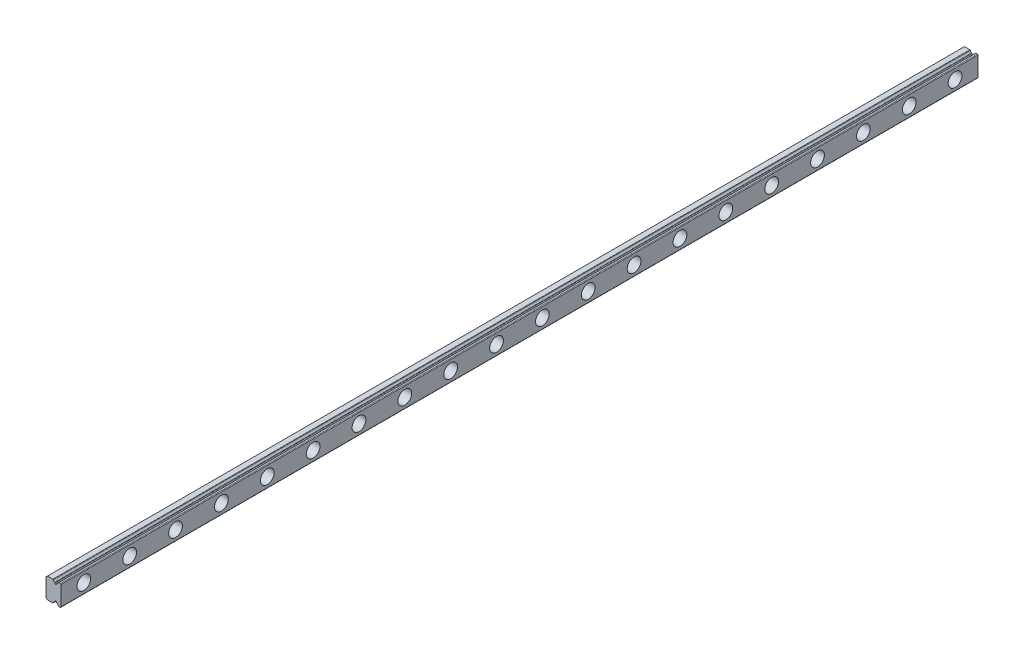
SolidWorks part; units mm, degrees
material "AISI 304"
ref_plane "前视基准面" through (0, 0, 0) normal (0, 0, 1) x (1, 0, 0)
ref_plane "上视基准面" through (0, 0, 0) normal (0, 1, 0) x (1, 0, 0)
ref_plane "右视基准面" through (0, 0, 0) normal (1, 0, 0) x (0, 0, -1)
sketch "草图1" plane through (0, 0, 0) normal (0, 0, 1) x (1, 0, 0)
  line L0 (0, 8.4) -> (0.6, 9)
  line L1 (0.6, 0) -> (2.9423, 0)
  line L2 (0, 0.6) -> (0, 8.4)
  line L3 (0.6, 9) -> (2.9423, 9)
  line L4 (6.5, 0.3) -> (6.5, 8.7)
  line L5 (0, 0.6) -> (0.6, 0)
  line L6 (4.25, 9) -> (4.25, 8) construction
  line L7 (4.25, 9) -> (4.25, 9.3) construction
  line L8 (3.85, 8) -> (3.85, 8.0351)
  line L9 (4.65, 8) -> (4.65, 8.0351)
  line L10 (5.5577, 9) -> (6.2, 9)
  line L11 (6.5, 4.5) -> (0, 4.5) construction
  line L12 (3.85, 8) -> (3.85, 8.0351)
  line L13 (4.65, 8) -> (4.65, 8.0351)
  line L14 (4.25, 0) -> (4.25, -0.3) construction
  line L15 (4.25, 0) -> (4.25, 1) construction
  line L16 (4.65, 1) -> (4.65, 0.9649)
  line L17 (3.85, 1) -> (3.85, 0.9649)
  line L18 (4.65, 1) -> (4.65, 0.9649)
  line L19 (3.85, 1) -> (3.85, 0.9649)
  line L20 (5.5577, 0) -> (6.2, 0)
  arc A0 (3.85, 8) -> (4.65, 8) centre (4.25, 8) ccw
  arc A1 (3.1291, 8.8714) -> (3.7357, 8.2158) centre (4.25, 9.3) ccw
  arc A2 (4.7643, 8.2158) -> (5.3709, 8.8714) centre (4.25, 9.3) ccw
  arc A3 (5.3709, 8.8714) -> (5.5577, 9) centre (5.5577, 8.8) cw
  arc A4 (4.65, 8.0351) -> (4.7643, 8.2158) centre (4.85, 8.0351) cw
  arc A5 (3.85, 8.0351) -> (3.7357, 8.2158) centre (3.65, 8.0351) ccw
  arc A6 (3.1291, 8.8714) -> (2.9423, 9) centre (2.9423, 8.8) ccw
  arc A7 (3.1291, 8.8714) -> (2.9423, 9) centre (2.9423, 8.8) ccw
  arc A8 (5.3709, 8.8714) -> (5.5577, 9) centre (5.5577, 8.8) cw
  arc A9 (4.65, 8.0351) -> (4.7643, 8.2158) centre (4.85, 8.0351) cw
  arc A10 (3.85, 8.0351) -> (3.7357, 8.2158) centre (3.65, 8.0351) ccw
  arc A11 (3.7357, 8.2158) -> (3.1291, 8.8714) centre (4.25, 9.3) cw
  arc A12 (5.3709, 8.8714) -> (4.7643, 8.2158) centre (4.25, 9.3) cw
  arc A13 (5.3709, 0.1286) -> (5.5577, 0) centre (5.5577, 0.2) ccw
  arc A14 (3.1291, 0.1286) -> (2.9423, 0) centre (2.9423, 0.2) cw
  arc A15 (5.3709, 0.1286) -> (4.7643, 0.7842) centre (4.25, -0.3) ccw
  arc A16 (3.7357, 0.7842) -> (3.1291, 0.1286) centre (4.25, -0.3) ccw
  arc A17 (3.85, 0.9649) -> (3.7357, 0.7842) centre (3.65, 0.9649) cw
  arc A18 (4.65, 0.9649) -> (4.7643, 0.7842) centre (4.85, 0.9649) ccw
  arc A19 (3.85, 0.9649) -> (3.7357, 0.7842) centre (3.65, 0.9649) cw
  arc A20 (4.65, 0.9649) -> (4.7643, 0.7842) centre (4.85, 0.9649) ccw
  arc A21 (4.7643, 0.7842) -> (5.3709, 0.1286) centre (4.25, -0.3) cw
  arc A22 (3.1291, 0.1286) -> (3.7357, 0.7842) centre (4.25, -0.3) cw
  arc A23 (3.85, 1) -> (4.65, 1) centre (4.25, 1) cw
  arc A24 (6.2, 0) -> (6.5, 0.3) centre (6.2, 0.3) ccw
  arc A25 (6.2, 9) -> (6.5, 8.7) centre (6.2, 8.7) cw
  point P0 (0, 0)
  point P2 (0, 9)
  point P24 (5.4119, 9)
  point P27 (4.65, 8.1686)
  point P49 (4.65, 0.8314)
  point P50 (5.4119, 0)
  point P53 (6.5, 0)
  dimension "D3" = 1
  dimension "D7" = 0.8
  dimension "D9" = 2.4
  dimension "D10" = 0.2
  dimension "D11" = 0.3
  dimension "D1" = 6.5
  dimension "D2" = 9
  dimension "D4" = 2.25
  dimension "D8" = 0.3
extrude "凸台-拉伸1" add sketch "草图1" along normal blind 400 contours A25 L10 A3 A2 A4 L9 A0 L8 A5 A1 A6 L3 L0 L2 L5 L1 A14 A16 A17 L17 A23 L16 A18 A15 A13 L20 A24 L4 region at (3.1975, 4.5, 0)
sketch "草图2" plane through (6.5, 0, 0) normal (1, 0, 0) x (0, 0, -1)
  line L0 (-400, 4.5) -> (-390, 4.5) construction
  line L1 (-400, 0.3) -> (-400, 8.7) construction
  line L2 (-390, 4.5) -> (-10, 4.5) construction
  line L3 (-10, 4.5) -> (0, 4.5) construction
  line L4 (0, 0.3) -> (0, 8.7) construction
  line L5 (-10, 4.5) -> (-30, 4.5) construction
  circle A0 centre (-10, 4.5) radius 3
  circle A1 centre (-30, 4.5) radius 3
  circle A2 centre (-50, 4.5) radius 3
  circle A3 centre (-70, 4.5) radius 3
  circle A4 centre (-90, 4.5) radius 3
  circle A5 centre (-110, 4.5) radius 3
  circle A6 centre (-130, 4.5) radius 3
  circle A7 centre (-150, 4.5) radius 3
  circle A8 centre (-170, 4.5) radius 3
  circle A9 centre (-190, 4.5) radius 3
  circle A10 centre (-210, 4.5) radius 3
  circle A11 centre (-230, 4.5) radius 3
  circle A12 centre (-250, 4.5) radius 3
  circle A13 centre (-270, 4.5) radius 3
  circle A14 centre (-290, 4.5) radius 3
  circle A15 centre (-310, 4.5) radius 3
  circle A16 centre (-330, 4.5) radius 3
  circle A17 centre (-350, 4.5) radius 3
  circle A18 centre (-370, 4.5) radius 3
  circle A19 centre (-390, 4.5) radius 3
  circle A20 centre (-410, 4.5) radius 3
  circle A21 centre (-430, 4.5) radius 3
  circle A22 centre (-450, 4.5) radius 3
  circle A23 centre (-470, 4.5) radius 3
  circle A24 centre (-490, 4.5) radius 3
  circle A25 centre (-510, 4.5) radius 3
  circle A26 centre (-530, 4.5) radius 3
  circle A27 centre (-550, 4.5) radius 3
  circle A28 centre (-570, 4.5) radius 3
  circle A29 centre (-590, 4.5) radius 3
  circle A30 centre (-610, 4.5) radius 3
  circle A31 centre (-630, 4.5) radius 3
  circle A32 centre (-650, 4.5) radius 3
  circle A33 centre (-670, 4.5) radius 3
  circle A34 centre (-690, 4.5) radius 3
  circle A35 centre (-710, 4.5) radius 3
  circle A36 centre (-730, 4.5) radius 3
  circle A37 centre (-750, 4.5) radius 3
  circle A38 centre (-770, 4.5) radius 3
  circle A39 centre (-790, 4.5) radius 3
  circle A40 centre (-810, 4.5) radius 3
  circle A41 centre (-830, 4.5) radius 3
  circle A42 centre (-850, 4.5) radius 3
  circle A43 centre (-870, 4.5) radius 3
  circle A44 centre (-890, 4.5) radius 3
  circle A45 centre (-910, 4.5) radius 3
  circle A46 centre (-930, 4.5) radius 3
  circle A47 centre (-950, 4.5) radius 3
  circle A48 centre (-970, 4.5) radius 3
  circle A49 centre (-990, 4.5) radius 3
  circle A50 centre (-1010, 4.5) radius 3
  circle A51 centre (-1030, 4.5) radius 3
  circle A52 centre (-1050, 4.5) radius 3
  circle A53 centre (-1070, 4.5) radius 3
  circle A54 centre (-1090, 4.5) radius 3
  circle A55 centre (-1110, 4.5) radius 3
  circle A56 centre (-1130, 4.5) radius 3
  circle A57 centre (-1150, 4.5) radius 3
  circle A58 centre (-1170, 4.5) radius 3
  circle A59 centre (-1190, 4.5) radius 3
  circle A60 centre (-1210, 4.5) radius 3
  circle A61 centre (-1230, 4.5) radius 3
  circle A62 centre (-1250, 4.5) radius 3
  circle A63 centre (-1270, 4.5) radius 3
  circle A64 centre (-1290, 4.5) radius 3
  circle A65 centre (-1310, 4.5) radius 3
  circle A66 centre (-1330, 4.5) radius 3
  circle A67 centre (-1350, 4.5) radius 3
  circle A68 centre (-1370, 4.5) radius 3
  circle A69 centre (-1390, 4.5) radius 3
  circle A70 centre (-1410, 4.5) radius 3
  circle A71 centre (-1430, 4.5) radius 3
  circle A72 centre (-1450, 4.5) radius 3
  circle A73 centre (-1470, 4.5) radius 3
  circle A74 centre (-1490, 4.5) radius 3
  circle A75 centre (-1510, 4.5) radius 3
  circle A76 centre (-1530, 4.5) radius 3
  circle A77 centre (-1550, 4.5) radius 3
  circle A78 centre (-1570, 4.5) radius 3
  circle A79 centre (-1590, 4.5) radius 3
  circle A80 centre (-1610, 4.5) radius 3
  circle A81 centre (-1630, 4.5) radius 3
  circle A82 centre (-1650, 4.5) radius 3
  circle A83 centre (-1670, 4.5) radius 3
  circle A84 centre (-1690, 4.5) radius 3
  circle A85 centre (-1710, 4.5) radius 3
  circle A86 centre (-1730, 4.5) radius 3
  circle A87 centre (-1750, 4.5) radius 3
  circle A88 centre (-1770, 4.5) radius 3
  circle A89 centre (-1790, 4.5) radius 3
  circle A90 centre (-1810, 4.5) radius 3
  circle A91 centre (-1830, 4.5) radius 3
  circle A92 centre (-1850, 4.5) radius 3
  circle A93 centre (-1870, 4.5) radius 3
  circle A94 centre (-1890, 4.5) radius 3
  circle A95 centre (-1910, 4.5) radius 3
  circle A96 centre (-1930, 4.5) radius 3
  circle A97 centre (-1950, 4.5) radius 3
  circle A98 centre (-1970, 4.5) radius 3
  circle A99 centre (-1990, 4.5) radius 3
  circle A100 centre (-2010, 4.5) radius 3
  circle A101 centre (-2030, 4.5) radius 3
  circle A102 centre (-2050, 4.5) radius 3
  circle A103 centre (-2070, 4.5) radius 3
  circle A104 centre (-2090, 4.5) radius 3
  circle A105 centre (-2110, 4.5) radius 3
  circle A106 centre (-2130, 4.5) radius 3
  circle A107 centre (-2150, 4.5) radius 3
  circle A108 centre (-2170, 4.5) radius 3
  circle A109 centre (-2190, 4.5) radius 3
  circle A110 centre (-2210, 4.5) radius 3
  circle A111 centre (-2230, 4.5) radius 3
  circle A112 centre (-2250, 4.5) radius 3
  circle A113 centre (-2270, 4.5) radius 3
  circle A114 centre (-2290, 4.5) radius 3
  circle A115 centre (-2310, 4.5) radius 3
  circle A116 centre (-2330, 4.5) radius 3
  circle A117 centre (-2350, 4.5) radius 3
  circle A118 centre (-2370, 4.5) radius 3
  circle A119 centre (-2390, 4.5) radius 3
  circle A120 centre (-2410, 4.5) radius 3
  circle A121 centre (-2430, 4.5) radius 3
  circle A122 centre (-2450, 4.5) radius 3
  circle A123 centre (-2470, 4.5) radius 3
  dimension "D2" = 6
  dimension "D1" = 10
  dimension "D4" = 20
  dimension "D3" = 25
  dimension "D5" = 100
extrude "切除-拉伸1" cut sketch "草图2" against normal blind 4.5
sketch "草图3" plane through (2, 0, 0) normal (1, 0, 0) x (0, 0, -1)
  line L0 (-10, 4.5) -> (-30, 4.5) construction
  circle A0 centre (-10, 4.5) radius 1.75
  circle A1 centre (-30, 4.5) radius 1.75
  circle A2 centre (-50, 4.5) radius 1.75
  circle A3 centre (-70, 4.5) radius 1.75
  circle A4 centre (-90, 4.5) radius 1.75
  circle A5 centre (-110, 4.5) radius 1.75
  circle A6 centre (-130, 4.5) radius 1.75
  circle A7 centre (-150, 4.5) radius 1.75
  circle A8 centre (-170, 4.5) radius 1.75
  circle A9 centre (-190, 4.5) radius 1.75
  circle A10 centre (-210, 4.5) radius 1.75
  circle A11 centre (-230, 4.5) radius 1.75
  circle A12 centre (-250, 4.5) radius 1.75
  circle A13 centre (-270, 4.5) radius 1.75
  circle A14 centre (-290, 4.5) radius 1.75
  circle A15 centre (-310, 4.5) radius 1.75
  circle A16 centre (-330, 4.5) radius 1.75
  circle A17 centre (-350, 4.5) radius 1.75
  circle A18 centre (-370, 4.5) radius 1.75
  circle A19 centre (-390, 4.5) radius 1.75
  circle A20 centre (-410, 4.5) radius 1.75
  circle A21 centre (-430, 4.5) radius 1.75
  circle A22 centre (-450, 4.5) radius 1.75
  circle A23 centre (-470, 4.5) radius 1.75
  circle A24 centre (-490, 4.5) radius 1.75
  circle A25 centre (-510, 4.5) radius 1.75
  circle A26 centre (-530, 4.5) radius 1.75
  circle A27 centre (-550, 4.5) radius 1.75
  circle A28 centre (-570, 4.5) radius 1.75
  circle A29 centre (-590, 4.5) radius 1.75
  circle A30 centre (-610, 4.5) radius 1.75
  circle A31 centre (-630, 4.5) radius 1.75
  circle A32 centre (-650, 4.5) radius 1.75
  circle A33 centre (-670, 4.5) radius 1.75
  circle A34 centre (-690, 4.5) radius 1.75
  circle A35 centre (-710, 4.5) radius 1.75
  circle A36 centre (-730, 4.5) radius 1.75
  circle A37 centre (-750, 4.5) radius 1.75
  circle A38 centre (-770, 4.5) radius 1.75
  circle A39 centre (-790, 4.5) radius 1.75
  circle A40 centre (-810, 4.5) radius 1.75
  circle A41 centre (-830, 4.5) radius 1.75
  circle A42 centre (-850, 4.5) radius 1.75
  circle A43 centre (-870, 4.5) radius 1.75
  circle A44 centre (-890, 4.5) radius 1.75
  circle A45 centre (-910, 4.5) radius 1.75
  circle A46 centre (-930, 4.5) radius 1.75
  circle A47 centre (-950, 4.5) radius 1.75
  circle A48 centre (-970, 4.5) radius 1.75
  circle A49 centre (-990, 4.5) radius 1.75
  circle A50 centre (-1010, 4.5) radius 1.75
  circle A51 centre (-1030, 4.5) radius 1.75
  circle A52 centre (-1050, 4.5) radius 1.75
  circle A53 centre (-1070, 4.5) radius 1.75
  dimension "D1" = 3.5
  dimension "D3" = 20
  dimension "D2" = 25
  dimension "D4" = 30
extrude "切除-拉伸2" cut sketch "草图3" against normal through all
